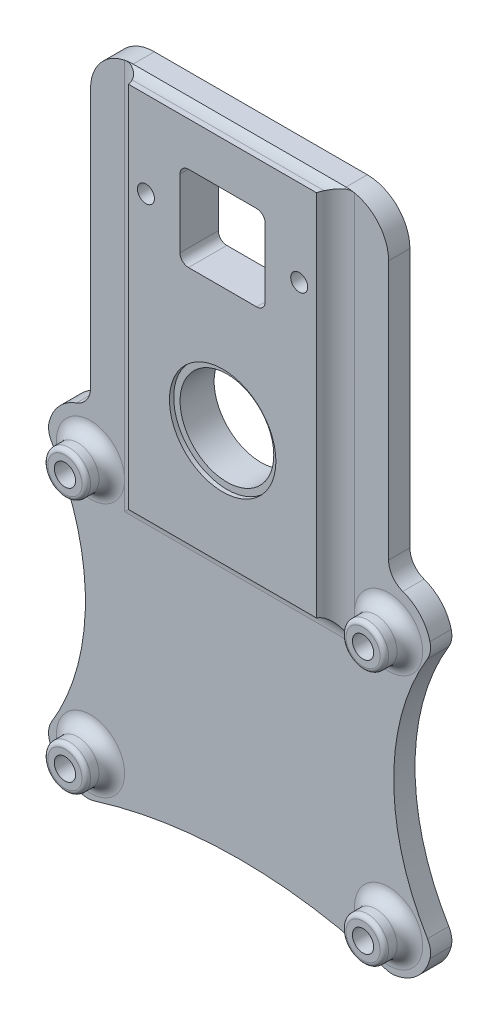
SolidWorks part; units mm, degrees
ref_plane "Front Plane" through (0, 0, 0) normal (0, 0, 1) x (1, 0, 0)
ref_plane "Top Plane" through (0, 0, 0) normal (0, 1, 0) x (1, 0, 0)
ref_plane "Right Plane" through (0, 0, 0) normal (1, 0, 0) x (0, 0, -1)
sketch "Sketch1" plane through (0, 0, 0) normal (0, 0, 1) x (1, 0, 0)
  line L0 (-35, -30.3) -> (35, -30.3) construction
  line L1 (-35, 29.5) -> (35, 29.5) construction
  line L2 (0, 40) -> (0, -55.1813) construction
  line L3 (-35, 40) -> (35, 40)
  circle A0 centre (-35, 29.5) radius 2.5
  circle A1 centre (35, 29.5) radius 2.5
  circle A2 centre (-35, -30.3) radius 2.5
  circle A3 centre (35, -30.3) radius 2.5
  arc A4 (35, 40) -> (45, 30) centre (35, 30) cw
  arc A5 (45, -29.6893) -> (35.245, -39.6893) centre (35, -29.6923) cw
  arc A6 (-35, -39.6893) -> (-45, -29.6893) centre (-35, -29.6893) cw
  arc A7 (-45, 30) -> (-35, 40) centre (-35, 30) cw
  arc A8 (-45, 30) -> (-45, -29.6893) centre (-91.1985, 0.1554) cw
  arc A9 (45, 30) -> (45, -29.6893) centre (91.1985, 0.1554) ccw
  arc A10 (-35, -39.6893) -> (35.245, -39.6893) centre (0.1225, -149.1946) cw
  point P0 (0, 0)
  point P6 (0, 0)
  point P18 (45, 40)
  dimension "D5" = 10
  dimension "D1" = 10.5
  dimension "D3" = 59.8
  dimension "D4" = 70
extrude "Boss-Extrude1" add sketch "Sketch1" along normal blind 5
sketch "Sketch2" plane through (0, 0, 5) normal (0, 0, 1) x (1, 0, 0)
  circle A0 centre (-35, 29.5) radius 5.0046
  circle A1 centre (35, 29.5) radius 5
  circle A2 centre (-35, -30.3) radius 5
  circle A3 centre (35, -30.3) radius 5
  circle A4 centre (-35, 29.5) radius 2.5
  circle A5 centre (35, 29.5) radius 2.5
  circle A6 centre (35, -30.3) radius 2.5
  circle A7 centre (-35, -30.3) radius 2.5
extrude "Boss-Extrude2" add sketch "Sketch2" along normal blind 6
chamfer "Chamfer1" distance 3 angle 45 4 edges at (37.5, -30.3, 0) (-32.5, -30.3, 0) (-32.5, 29.5, 0) (37.5, 29.5, 0)
fillet "Fillet1" radius 3 4 edges at (-40, -30.3, 5) (30, -30.3, 5) (30, 29.5, 5) (-40.0046, 29.5, 5)
fillet "Fillet2" radius 1 4 edges at (-30, -30.3, 11) (40, -30.3, 11) (40, 29.5, 11) (-29.9954, 29.5, 11)
fillet "Fillet3" radius 5 6 edges at (45, 30, 2.5) (45, -29.6893, 2.5) (35.245, -39.6893, 2.5) (-35, -39.6893, 2.5) (-45, -29.6893, 2.5) (-45, 30, 2.5)
sketch "Sketch3" plane through (0, 0, 0) normal (0, 0, -1) x (-1, 0, 0)
  line L1 (-35, 40) -> (35, 40)
  line L2 (-35, 40) -> (-35, 105)
  line L3 (-25, 115) -> (25, 115)
  line L4 (35, 40) -> (35, 105)
  arc A0 (35, 105) -> (25, 115) centre (25, 105) ccw
  arc A1 (-25, 115) -> (-35, 105) centre (-25, 105) ccw
  point P9 (-35, 115)
  dimension "D2" = 10
  dimension "D1" = 75
extrude "Boss-Extrude3" add sketch "Sketch3" against normal blind 5
fillet "Fillet4" radius 5 2 edges at (-35, 40, 2.5) (35, 40, 2.5)
sketch "Sketch6" plane through (0, 0, 5) normal (0, 0, 1) x (1, 0, 0)
  line L1 (-22.0604, 27.8912) -> (22.0604, 27.8912)
  line L2 (-22.0604, 27.8912) -> (-22.0604, 114.3656)
  line L3 (-22.0604, 114.3656) -> (22.0604, 114.3656)
  line L4 (22.0604, 27.8912) -> (22.0604, 114.3656)
  line L5 (-22.0604, 27.8912) -> (22.0604, 114.3656) construction
  line L6 (-22.0604, 114.3656) -> (22.0604, 27.8912) construction
  point P0 (0, 71.1284)
extrude "Boss-Extrude4" add sketch "Sketch6" along normal blind 4
sketch "Sketch4" plane through (0, 0, 0) normal (0, 0, 1) x (1, 0, 0)
  line L0 (0, 115) -> (0.0863, -34.1946) construction
  line L1 (-7.9879, 84.1306) -> (8.0121, 84.1306)
  line L2 (-9.9879, 86.1306) -> (-9.9879, 102.1306)
  line L3 (-7.9879, 104.1306) -> (8.0121, 104.1306)
  line L4 (10.0121, 86.1306) -> (10.0121, 102.1306)
  line L5 (-9.9879, 84.1306) -> (10.0121, 104.1306) construction
  line L6 (-9.9879, 104.1306) -> (10.0121, 84.1306) construction
  line L7 (-25, 115) -> (25, 115) construction
  arc A0 (34.3274, -39.3992) -> (-34.1514, -39.4207) centre (0.1225, -149.1946) ccw construction
  arc A1 (-9.9879, 86.1306) -> (-7.9879, 84.1306) centre (-7.9879, 86.1306) ccw
  arc A2 (8.0121, 84.1306) -> (10.0121, 86.1306) centre (8.0121, 86.1306) ccw
  arc A3 (10.0121, 102.1306) -> (8.0121, 104.1306) centre (8.0121, 102.1306) ccw
  arc A4 (-7.9879, 104.1306) -> (-9.9879, 102.1306) centre (-7.9879, 102.1306) ccw
  circle A9 centre (0.0347, 55) radius 11
  point P0 (0.0121, 94.1306)
  dimension "D3" = 2
  dimension "D4" = 60
  dimension "D1" = 20
  dimension "D2" = 20
extrude "Cut-Extrude1" cut sketch "Sketch4" along normal up to next
fillet "Fillet5" radius 5 3 edges at (22.0604, 71.1284, 5) (0, 27.8912, 5) (-22.0604, 71.1284, 5)
sketch "Sketch7" plane through (0, 104.1306, 0) normal (0, -1, 0) x (1, 0, 0)
  line L0 (-7.9879, 9) -> (8.0121, 9) construction
  circle A0 centre (0.0102, 4.5) radius 2
  dimension "D1" = 4.5
extrude "Cut-Extrude2" [suppressed] cut sketch "Sketch7" against normal up to next
sketch "Sketch8" [suppressed] plane through (0, 114.3656, 0) normal (0, 1, 0) x (1, 0, 0)
  circle A0 centre (0.0102, -4.5) radius 3.2
extrude "Cut-Extrude3" [suppressed] cut sketch "Sketch8" along normal up to next and the other way blind 1
fillet "Fillet7" radius 6 1 edges at (0, 114.3656, 5)
sketch "Sketch9" plane through (0, 0, 0) normal (0, 0, -1) x (-1, 0, 0)
  line L0 (-21.4894, 94.1306) -> (23.3996, 94.1306) construction
  line L1 (-8.0121, 104.1306) -> (7.9879, 104.1306) construction
  line L2 (-0.0121, 104.1306) -> (-0.0121, 84.1306) construction
  line L3 (7.9879, 84.1306) -> (-8.0121, 84.1306) construction
  circle A0 centre (-18.0121, 94.1306) radius 2
  circle A1 centre (17.9879, 94.1306) radius 2
  dimension "D1" = 18
  dimension "D2" = 18
extrude "Cut-Extrude4" cut sketch "Sketch9" against normal up to next
sketch "Sketch10" plane through (0, 0, 0) normal (0, 0, 1) x (1, 0, 0)
  line L1 (-13.9465, 94.1306) -> (-15.9672, 97.6306)
  line L2 (-15.9672, 97.6306) -> (-20.0086, 97.6306)
  line L3 (-20.0086, 97.6306) -> (-22.0294, 94.1306)
  line L4 (-22.0294, 94.1306) -> (-20.0086, 90.6306)
  line L5 (-20.0086, 90.6306) -> (-15.9672, 90.6306)
  line L6 (-15.9672, 90.6306) -> (-13.9465, 94.1306)
  line L7 (13.9706, 94.1306) -> (15.9914, 90.6306)
  line L8 (15.9914, 90.6306) -> (20.0328, 90.6306)
  line L9 (20.0328, 90.6306) -> (22.0535, 94.1306)
  line L10 (22.0535, 94.1306) -> (20.0328, 97.6306)
  line L11 (20.0328, 97.6306) -> (15.9914, 97.6306)
  line L12 (15.9914, 97.6306) -> (13.9706, 94.1306)
  circle A0 centre (-17.9879, 94.1306) radius 3.5 construction
  circle A1 centre (18.0121, 94.1306) radius 3.5 construction
sketch "Sketch11" plane through (0, 0, 9) normal (0, 0, 1) x (1, 0, 0)
  circle A0 centre (0.0347, 55) radius 12.5
extrude "Cut-Extrude6" cut sketch "Sketch11" against normal blind 1
extrude "Cut-Extrude7" cut sketch "Sketch10" along normal blind 1.5
